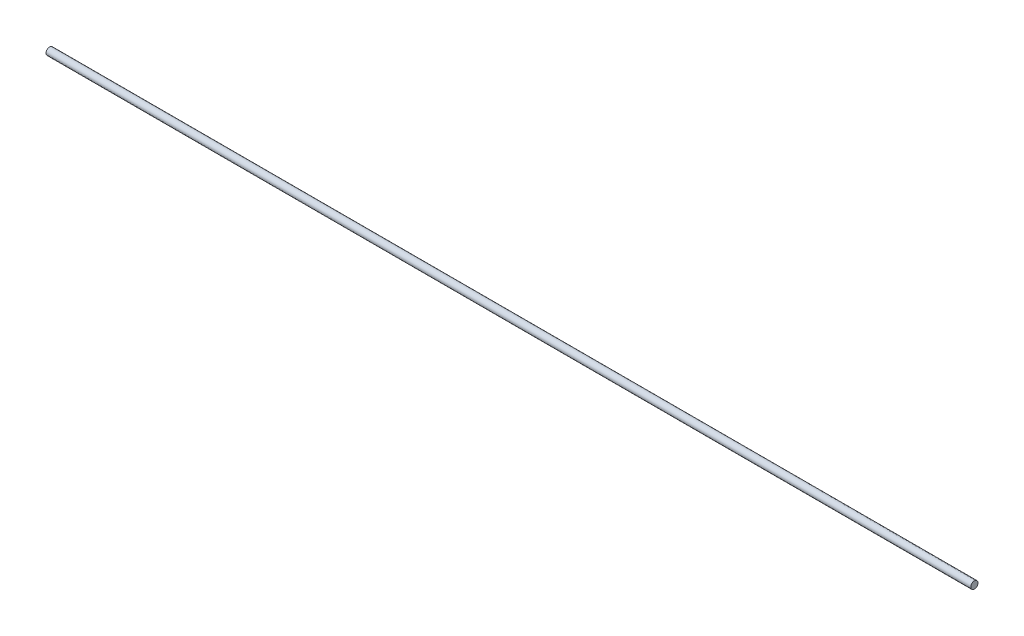
SolidWorks part; units mm, degrees
material "Hexcel AS4C (3000 Filaments)"
ref_plane "Front Plane" through (0, 0, 0) normal (0, 0, 1) x (1, 0, 0)
ref_plane "Top Plane" through (0, 0, 0) normal (0, 1, 0) x (1, 0, 0)
ref_plane "Right Plane" through (0, 0, 0) normal (1, 0, 0) x (0, 0, -1)
sketch "Sketch1" plane through (0, 0, 0) normal (1, 0, 0) x (0, 0, -1)
  circle A1 centre (0, 0) radius 3.175
  point P1 (0, 0)
  dimension "D1" = 6.35
extrude "Boss-Extrude1" add sketch "Sketch1" along normal blind 812.8 contours A1
